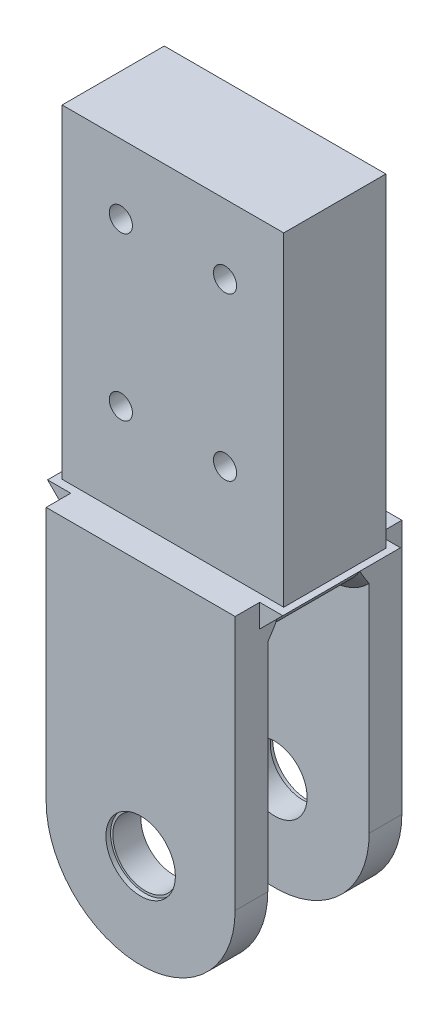
SolidWorks part; units mm, degrees
ref_plane "Front Plane" through (0, 0, 0) normal (0, 0, 1) x (1, 0, 0)
ref_plane "Top Plane" through (0, 0, 0) normal (0, 1, 0) x (1, 0, 0)
ref_plane "Right Plane" through (0, 0, 0) normal (1, 0, 0) x (0, 0, -1)
sketch "Sketch1" plane through (0, 0, 0) normal (0, 0, 1) x (1, 0, 0)
  line L0 (-25.4, 0) -> (-25.4, 125)
  line L1 (-25.4, 125) -> (25.4, 125)
  line L2 (25.4, 125) -> (25.4, 0)
  line L4 (-11.25, 110) -> (11.25, 110) construction
  line L5 (-11.25, 110) -> (-11.25, 75) construction
  line L6 (-11.25, 75) -> (11.25, 75) construction
  line L7 (11.25, 110) -> (11.25, 75) construction
  circle A0 centre (0, 0) radius 7
  arc A1 (-25.4, 0) -> (25.4, 0) centre (0, 0) ccw
  circle A2 centre (-11.25, 110) radius 2.5
  circle A3 centre (11.25, 110) radius 2.5
  circle A4 centre (11.25, 75) radius 2.5
  circle A5 centre (-11.25, 75) radius 2.5
  point P13 (0, 75)
  dimension "D1" = 14
  dimension "D4" = 5
  dimension "D2" = 50.8
  dimension "D3" = 125
  dimension "D5" = 35
  dimension "D6" = 15
  dimension "D7" = 22.5
extrude "Boss-Extrude1" add sketch "Sketch1" along normal mid plane 36
sketch "Sketch2" plane through (25.4, 0, 0) normal (1, 0, 0) x (0, 0, -1)
  line L0 (-18, -25.4) -> (18, -25.4) construction
  line L1 (-10.95, 45) -> (10.95, 45)
  line L2 (-10.95, 45) -> (-10.95, -25.4)
  line L3 (-10.95, -25.4) -> (10.95, -25.4)
  line L4 (10.95, 45) -> (10.95, -25.4)
  line L5 (-18, 0) -> (18, 0) construction
  point P8 (0, 0)
  point P9 (0, 45)
  dimension "D1" = 21.9
  dimension "D2" = 45
extrude "Cut-Extrude1" cut sketch "Sketch2" against normal through all
sketch "Sketch3" plane through (0, 0, 18) normal (0, 0, 1) x (1, 0, 0)
  circle A0 centre (0, 0) radius 7.5
  dimension "D1" = 15
extrude "Cut-Extrude2" cut sketch "Sketch3" against normal blind 1
sketch "Sketch4" plane through (0, 0, -18) normal (0, 0, -1) x (-1, 0, 0)
  circle A0 centre (0, 0) radius 7.5
  dimension "D1" = 15
extrude "Cut-Extrude3" cut sketch "Sketch4" against normal blind 1
sketch "Sketch5" plane through (25.4, 0, 0) normal (1, 0, 0) x (0, 0, -1)
  line L1 (-18, 125) -> (-12.7, 125)
  line L2 (-18, 125) -> (-18, 55)
  line L3 (-18, 55) -> (-12.7, 55)
  line L4 (-12.7, 125) -> (-12.7, 55)
  line L5 (18, 125) -> (12.7, 125)
  line L6 (18, 125) -> (18, 55)
  line L7 (18, 55) -> (12.7, 55)
  line L8 (12.7, 125) -> (12.7, 55)
  dimension "D1" = 70
  dimension "D2" = 25.4
extrude "Cut-Extrude4" cut sketch "Sketch5" against normal through all
sketch "Sketch6" plane through (0, 0, 18) normal (0, 0, 1) x (1, 0, 0)
  line L0 (-20.4, 0) -> (-20.4, 55)
  line L1 (-25.4, 55) -> (25.4, 55) construction
  line L3 (-25.4, 55) -> (25.4, 55) construction
  line L4 (20.4, 55) -> (20.4, 0)
  line L5 (-20.4, 55) -> (-25.4, 55)
  line L6 (-25.4, 55) -> (-25.4, -25.4)
  line L7 (-25.4, -25.4) -> (25.4, -25.4)
  line L8 (25.4, -25.4) -> (25.4, 55)
  line L9 (25.4, 55) -> (20.4, 55)
  arc A0 (-20.4, 0) -> (20.4, 0) centre (0, 0) ccw
  arc A1 (-25.4, 0) -> (25.4, 0) centre (0, 0) ccw construction
  point P19 (0, -25.4)
  dimension "D1" = 5
extrude "Cut-Extrude5" cut sketch "Sketch6" against normal through all
sketch "Sketch8" plane through (0, 125, 0) normal (0, 1, 0) x (1, 0, 0)
  line L0 (-25.4, -12.7) -> (-25.4, 12.7) construction
  line L1 (-23.925, 11.025) -> (23.925, 11.025)
  line L2 (-23.925, 11.025) -> (-23.925, -11.025)
  line L3 (-23.925, -11.025) -> (23.925, -11.025)
  line L4 (23.925, 11.025) -> (23.925, -11.025)
  line L6 (-25.4, 12.7) -> (25.4, 12.7)
  line L7 (-25.4, 12.7) -> (-25.4, -12.7)
  line L8 (-25.4, -12.7) -> (25.4, -12.7)
  line L9 (25.4, 12.7) -> (25.4, -12.7)
  point P5 (0, 11.025)
  point P10 (-25.4, 0)
  point P11 (-23.925, 0)
  dimension "D1" = 22.05
  dimension "D2" = 47.85
extrude "Cut-Extrude6" cut sketch "Sketch8" against normal up to surface (70 mm away) up to face at (0, 55, -15.35)
sketch "Sketch9" plane through (0, 55, 0) normal (0, 1, 0) x (1, 0, 0)
  line L0 (23.925, 11.025) -> (-23.925, 11.025) construction
  line L1 (-25.4, 12.7) -> (25.4, 12.7)
  line L2 (-25.4, 12.7) -> (-25.4, -12.7)
  line L3 (-25.4, -12.7) -> (25.4, -12.7)
  line L4 (25.4, 12.7) -> (25.4, -12.7)
  line L5 (-23.925, 11.025) -> (-23.925, -11.025) construction
  point P8 (0, 11.025)
  point P9 (0, 12.7)
  point P12 (-23.925, 0)
  point P13 (-25.4, 0)
  dimension "D1" = 25.4
  dimension "D2" = 50.8
extrude "Boss-Extrude2" add sketch "Sketch9" against normal blind 5
fillet "Fillet1" radius 10 2 edges at (20.4, 45, 0) (-20.4, 45, 0)
chamfer "Chamfer1" distance 5 angle 45 2 edges at (-25.4, 50, 0) (25.4, 50, 0)
chamfer "Chamfer2" distance 2 angle 45 6 edges at (-16.7397, 46.3397, -10.95) (16.7397, 46.3397, -10.95) (0, 45, -10.95) (-16.7397, 46.3397, 10.95) (16.7397, 46.3397, 10.95) (0, 45, 10.95)
